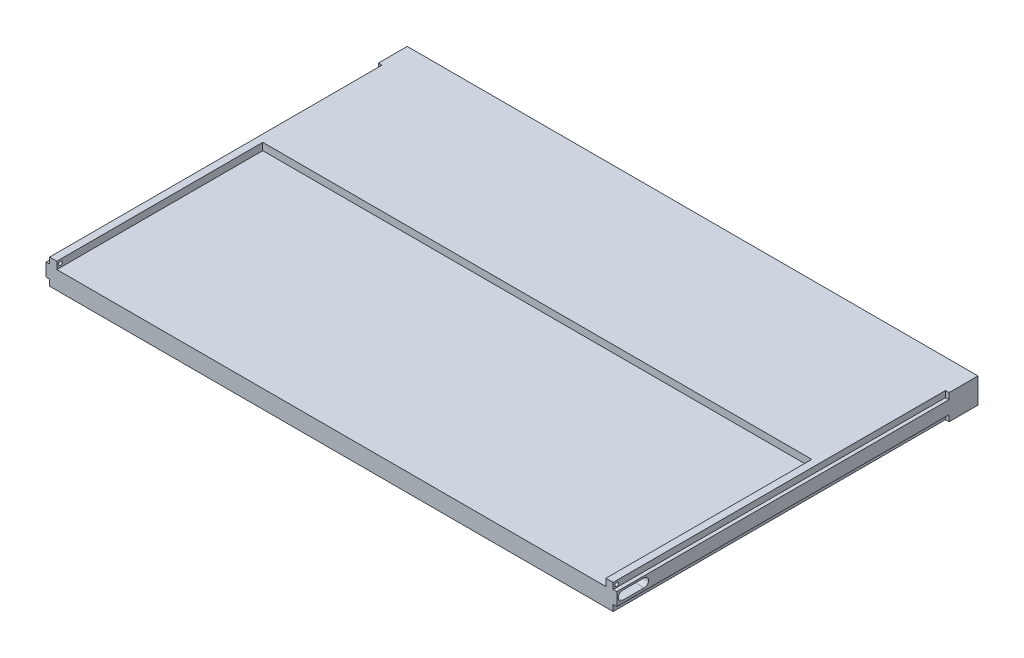
SolidWorks part; units mm, degrees
material "6061 Alloy"
ref_plane "Front Plane" through (0, 0, 0) normal (0, 0, 1) x (1, 0, 0)
ref_plane "Top Plane" through (0, 0, 0) normal (0, 1, 0) x (1, 0, 0)
ref_plane "Right Plane" through (0, 0, 0) normal (1, 0, 0) x (0, 0, -1)
sketch "Sketch1" plane through (0, 0, 0) normal (0, 1, 0) x (1, 0, 0)
  line L1 (-247.65, 158.75) -> (247.65, 158.75)
  line L2 (-247.65, 158.75) -> (-247.65, -158.75)
  line L3 (-247.65, -158.75) -> (247.65, -158.75)
  line L4 (247.65, 158.75) -> (247.65, -158.75)
  line L5 (-247.65, 158.75) -> (247.65, -158.75) construction
  line L6 (-247.65, -158.75) -> (247.65, 158.75) construction
  point P0 (0, 0)
  dimension "D1" = 495.3
  dimension "D2" = 317.5
extrude "Boss-Extrude1" add sketch "Sketch1" along normal blind 15.875
sketch "Sketch2" plane through (0, 15.875, 0) normal (0, 1, 0) x (1, 0, 0)
  line L0 (-247.65, -158.75) -> (247.65, -158.75) construction
  line L1 (-247.65, 158.75) -> (-241.3, 158.75)
  line L2 (-247.65, 158.75) -> (-247.65, -158.75)
  line L3 (-247.65, -158.75) -> (-241.3, -158.75)
  line L4 (-241.3, 22.225) -> (-241.3, -158.75)
  line L5 (247.65, 158.75) -> (-247.65, 158.75) construction
  line L6 (247.65, 158.75) -> (241.3, 158.75)
  line L7 (247.65, 158.75) -> (247.65, -158.75)
  line L8 (247.65, -158.75) -> (241.3, -158.75)
  line L9 (241.3, 22.225) -> (241.3, -158.75)
  line L10 (-241.3, 158.75) -> (241.3, 158.75)
  line L12 (-241.3, 22.225) -> (241.3, 22.225)
  point P14 (-244.475, -158.75)
  dimension "D1" = 6.35
  dimension "D2" = 180.975
extrude "Boss-Extrude2" add sketch "Sketch2" along normal blind 6.35
sketch "Sketch3" plane through (-247.65, 0, 0) normal (-1, 0, 0) x (0, 0, 1)
  line L0 (158.75, 22.225) -> (158.75, 0) construction
  line L1 (-158.75, 22.225) -> (158.75, 22.225) construction
  circle A0 centre (155.575, 19.05) radius 1.5875
  dimension "D3" = 3.175
  dimension "D1" = 3.175
  dimension "D2" = 3.175
extrude "Cut-Extrude1" cut sketch "Sketch3" against normal through all
sketch "Sketch4" plane through (0, 0, 158.75) normal (0, 0, 1) x (1, 0, 0)
  line L0 (-247.65, 22.225) -> (-247.65, 0) construction
  line L1 (-247.65, 16.8275) -> (-250.825, 16.8275)
  line L2 (-247.65, 16.8275) -> (-247.65, 5.3975)
  line L3 (-247.65, 5.3975) -> (-250.825, 5.3975)
  line L4 (-250.825, 16.8275) -> (-250.825, 5.3975)
  point P12 (-247.65, 11.1125)
  dimension "D1" = 11.43
  dimension "D2" = 3.175
extrude "Boss-Extrude3" add sketch "Sketch4" against normal blind 292.1
sketch "Sketch5" plane through (-247.65, 0, 0) normal (-1, 0, 0) x (0, 0, 1)
  line L0 (-158.75, 0) -> (158.75, 0) construction
  line L1 (-158.75, 22.225) -> (-133.35, 22.225)
  line L2 (-158.75, 22.225) -> (-158.75, 0)
  line L3 (-158.75, 0) -> (-133.35, 0)
  line L4 (-133.35, 22.225) -> (-133.35, 0)
  line L5 (-133.35, 5.3975) -> (-133.35, 16.8275) construction
extrude "Boss-Extrude4" add sketch "Sketch5" along normal up to surface (3.175 mm away) up to face at (-250.825, 11.1125, 12.7)
mirror "Mirror1" about plane through (0, 0, 0) normal (1, 0, 0) of "Boss-Extrude4", "Boss-Extrude3"
sketch "Sketch6" plane through (-247.65, 0, 0) normal (-1, 0, 0) x (0, 0, 1)
  line L0 (153.67, 11.43) -> (134.62, 11.43) construction
  line L1 (153.67, 7.62) -> (134.62, 7.62)
  line L2 (153.67, 15.24) -> (134.62, 15.24)
  line L3 (158.75, 5.3975) -> (158.75, 0) construction
  line L4 (-133.35, 0) -> (158.75, 0) construction
  arc A0 (153.67, 7.62) -> (153.67, 15.24) centre (153.67, 11.43) ccw
  arc A1 (134.62, 15.24) -> (134.62, 7.62) centre (134.62, 11.43) ccw
  point P2 (144.145, 11.43)
  dimension "D1" = 19.05
  dimension "D2" = 5.08
  dimension "D3" = 7.62
  dimension "D4" = 11.43
extrude "Cut-Extrude2" cut sketch "Sketch6" against normal blind 50.8 from surface starting at face at (-250.825, 11.1125, -66.675)
extrude "Cut-Extrude3" cut sketch "Sketch6<2>" along normal blind 25.4 from surface starting at face at (250.825, 11.1125, -66.675)
sketch "Sketch6<2>" plane through (-247.65, 0, 0) normal (-1, 0, 0) x (0, 0, 1) same geometry as "Sketch6"
